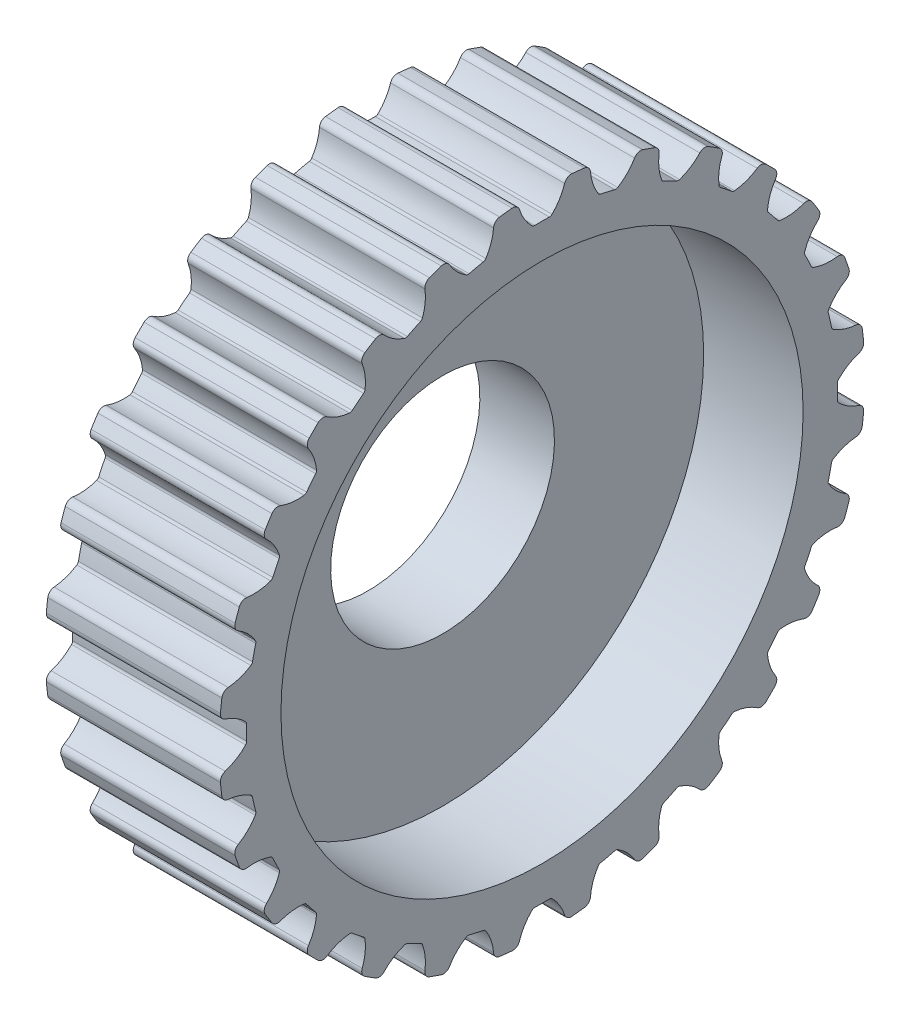
SolidWorks part; units mm, degrees
material "POM 乙缩醛共聚物"
ref_plane "前视基准面" through (0, 0, 0) normal (0, 0, 1) x (1, 0, 0)
ref_plane "上视基准面" through (0, 0, 0) normal (0, 1, 0) x (1, 0, 0)
ref_plane "右视基准面" through (0, 0, 0) normal (1, 0, 0) x (0, 0, -1)
ref_plane "基准面1" through (0, 0, 0) normal (0, 0, 1) x (1, 0, 0)
sketch "草图1" plane through (0, 0, 0) normal (0, 0, 1) x (1, 0, 0)
  line L0 (0, 0) -> (0, 10)
  line L1 (0, 10) -> (1, 10)
  line L2 (1, 10) -> (1, 12.8583)
  line L3 (1, 12.8583) -> (0.4955, 14.7412)
  line L4 (0.4955, 14.7412) -> (1.4614, 15)
  line L5 (1.4614, 15) -> (2, 12.99)
  line L6 (2, 12.99) -> (9, 12.99)
  line L7 (9, 12.99) -> (9.5386, 15)
  line L8 (9.5386, 15) -> (10.5045, 14.7412)
  line L9 (10.5045, 14.7412) -> (10, 12.8583)
  line L10 (10, 12.8583) -> (10, 10)
  line L11 (10, 10) -> (11, 10)
  line L12 (11, 10) -> (11, 0)
  line L13 (11, 0) -> (0, 0)
  line L14 (11, 0) -> (0, 0) construction
revolve "旋转1" add sketch "草图1" angle 360 about L14 reverse direction yes
ref_plane "基准面2" through (0, 0, 0) normal (0, 0, 1) x (1, 0, 0)
hole_wizard "孔1" positions "草图3" profile "草图2" legacy
sketch "草图3" plane through (11, 0, 0) normal (1, 0, 0) x (0, 0, -1)
  point P0 (0, 0)
sketch "草图2" plane through (11, 0, 0) normal (0, 1, 0) x (0, 0, -1)
  line L0 (0, 0) -> (0, 11)
  line L1 (0, 11) -> (4.5, 11)
  line L2 (4.5, 11) -> (4.5, 0)
  line L3 (4.5, 0) -> (0, 0)
  line L4 (0, 110) -> (0, -10) construction
  dimension "直径" = 9
  dimension "深度" = 11
ref_plane "基准面3" through (2, 0, 0) normal (1, 0, 0) x (0, 0, -1)
sketch "草图4" plane through (2, 0, 0) normal (1, 0, 0) x (0, 0, -1)
  circle A0 centre (0, 0) radius 17.99
  arc A1 (-12.9343, 1.2013) -> (-12.7398, 0.9084) centre (-12.6555, 1.1754) ccw
  arc A2 (-12.7398, 0.9084) -> (-11.9188, 0.4022) centre (-13.3344, -0.975) cw
  arc A3 (-11.9188, 0.4022) -> (-11.8764, 0.2939) centre (-12.0263, 0.2976) cw
  arc A4 (-11.8764, 0.2939) -> (-11.8764, -0.2939) centre (0, 0) ccw
  arc A5 (-11.8764, -0.2939) -> (-11.9188, -0.4022) centre (-12.0263, -0.2976) cw
  arc A6 (-11.9188, -0.4022) -> (-12.7398, -0.9084) centre (-13.3344, 0.975) cw
  arc A7 (-12.7398, -0.9084) -> (-12.9343, -1.2013) centre (-12.6555, -1.1754) ccw
  arc A8 (-12.9343, -1.2013) -> (-12.8774, -1.707) centre (0, 0) ccw
  arc A9 (-12.8774, -1.707) -> (-12.6225, -1.9493) centre (-12.5998, -1.6702) ccw
  arc A10 (-12.6225, -1.9493) -> (-11.7095, -2.2601) centre (-12.7831, -3.9177) cw
  arc A11 (-11.7095, -2.2601) -> (-11.644, -2.3562) centre (-11.791, -2.386) cw
  arc A12 (-11.644, -2.3562) -> (-11.5132, -2.9293) centre (0, 0) ccw
  arc A13 (-11.5132, -2.9293) -> (-11.5305, -3.0443) centre (-11.6586, -2.9663) cw
  arc A14 (-11.5305, -3.0443) -> (-12.2183, -3.7205) centre (-13.217, -2.0166) cw
  arc A15 (-12.2183, -3.7205) -> (-12.3427, -4.0493) centre (-12.0767, -3.962) ccw
  arc A16 (-12.3427, -4.0493) -> (-12.1746, -4.5297) centre (0, 0) ccw
  arc A17 (-12.1746, -4.5297) -> (-11.8723, -4.7092) centre (-11.9122, -4.432) ccw
  arc A18 (-11.8723, -4.7092) -> (-10.913, -4.809) centre (-11.5908, -6.664) cw
  arc A19 (-10.913, -4.809) -> (-10.8278, -4.8882) centre (-10.9645, -4.9499) cw
  arc A20 (-10.8278, -4.8882) -> (-10.5727, -5.4178) centre (0, 0) ccw
  arc A21 (-10.5727, -5.4178) -> (-10.564, -5.5338) centre (-10.7062, -5.4862) cw
  arc A22 (-10.564, -5.5338) -> (-11.0841, -6.346) centre (-12.4369, -4.9071) cw
  arc A23 (-11.0841, -6.346) -> (-11.1322, -6.6943) centre (-10.8923, -6.55) ccw
  arc A24 (-11.1322, -6.6943) -> (-10.8615, -7.1252) centre (0, 0) ccw
  arc A25 (-10.8615, -7.1252) -> (-10.5268, -7.233) centre (-10.6273, -6.9716) ccw
  arc A26 (-10.5268, -7.233) -> (-9.5693, -7.1168) centre (-9.8174, -9.0761) cw
  arc A27 (-9.5693, -7.1168) -> (-9.4686, -7.175) centre (-9.5881, -7.2656) cw
  arc A28 (-9.4686, -7.175) -> (-9.1021, -7.6346) centre (0, 0) ccw
  arc A29 (-9.1021, -7.6346) -> (-9.0677, -7.7457) centre (-9.217, -7.731) cw
  arc A30 (-9.0677, -7.7457) -> (-9.394, -8.6534) centre (-11.0332, -7.5516) cw
  arc A31 (-9.394, -8.6534) -> (-9.3635, -9.0036) centre (-9.1617, -8.8096) ccw
  arc A32 (-9.3635, -9.0036) -> (-9.0036, -9.3635) centre (0, 0) ccw
  arc A33 (-9.0036, -9.3635) -> (-8.6534, -9.394) centre (-8.8096, -9.1617) ccw
  arc A34 (-8.6534, -9.394) -> (-7.7457, -9.0677) centre (-7.5516, -11.0332) cw
  arc A35 (-7.7457, -9.0677) -> (-7.6346, -9.1021) centre (-7.731, -9.217) cw
  arc A36 (-7.6346, -9.1021) -> (-7.175, -9.4686) centre (0, 0) ccw
  arc A37 (-7.175, -9.4686) -> (-7.1168, -9.5693) centre (-7.2656, -9.5881) cw
  arc A38 (-7.1168, -9.5693) -> (-7.233, -10.5268) centre (-9.0761, -9.8174) cw
  arc A39 (-7.233, -10.5268) -> (-7.1252, -10.8615) centre (-6.9716, -10.6273) ccw
  arc A40 (-7.1252, -10.8615) -> (-6.6943, -11.1322) centre (0, 0) ccw
  arc A41 (-6.6943, -11.1322) -> (-6.346, -11.0841) centre (-6.55, -10.8923) ccw
  arc A42 (-6.346, -11.0841) -> (-5.5338, -10.564) centre (-4.9071, -12.4369) cw
  arc A43 (-5.5338, -10.564) -> (-5.4178, -10.5727) centre (-5.4862, -10.7062) cw
  arc A44 (-5.4178, -10.5727) -> (-4.8882, -10.8278) centre (0, 0) ccw
  arc A45 (-4.8882, -10.8278) -> (-4.809, -10.913) centre (-4.9499, -10.9645) cw
  arc A46 (-4.809, -10.913) -> (-4.7092, -11.8723) centre (-6.664, -11.5908) cw
  arc A47 (-4.7092, -11.8723) -> (-4.5297, -12.1746) centre (-4.432, -11.9122) ccw
  arc A48 (-4.5297, -12.1746) -> (-4.0493, -12.3427) centre (0, 0) ccw
  arc A49 (-4.0493, -12.3427) -> (-3.7205, -12.2183) centre (-3.962, -12.0767) ccw
  arc A50 (-3.7205, -12.2183) -> (-3.0443, -11.5305) centre (-2.0166, -13.217) cw
  arc A51 (-3.0443, -11.5305) -> (-2.9293, -11.5132) centre (-2.9663, -11.6586) cw
  arc A52 (-2.9293, -11.5132) -> (-2.3562, -11.644) centre (0, 0) ccw
  arc A53 (-2.3562, -11.644) -> (-2.2601, -11.7095) centre (-2.386, -11.791) cw
  arc A54 (-2.2601, -11.7095) -> (-1.9493, -12.6225) centre (-3.9177, -12.7831) cw
  arc A55 (-1.9493, -12.6225) -> (-1.707, -12.8774) centre (-1.6702, -12.5998) ccw
  arc A56 (-1.707, -12.8774) -> (-1.2013, -12.9343) centre (0, 0) ccw
  arc A57 (-1.2013, -12.9343) -> (-0.9084, -12.7398) centre (-1.1754, -12.6555) ccw
  arc A58 (-0.9084, -12.7398) -> (-0.4022, -11.9188) centre (0.975, -13.3344) cw
  arc A59 (-0.4022, -11.9188) -> (-0.2939, -11.8764) centre (-0.2976, -12.0263) cw
  arc A60 (-0.2939, -11.8764) -> (0.2939, -11.8764) centre (0, 0) ccw
  arc A61 (0.2939, -11.8764) -> (0.4022, -11.9188) centre (0.2976, -12.0263) cw
  arc A62 (0.4022, -11.9188) -> (0.9084, -12.7398) centre (-0.975, -13.3344) cw
  arc A63 (0.9084, -12.7398) -> (1.2013, -12.9343) centre (1.1754, -12.6555) ccw
  arc A64 (1.2013, -12.9343) -> (1.707, -12.8774) centre (0, 0) ccw
  arc A65 (1.707, -12.8774) -> (1.9493, -12.6225) centre (1.6702, -12.5998) ccw
  arc A66 (1.9493, -12.6225) -> (2.2601, -11.7095) centre (3.9177, -12.7831) cw
  arc A67 (2.2601, -11.7095) -> (2.3562, -11.644) centre (2.386, -11.791) cw
  arc A68 (2.3562, -11.644) -> (2.9293, -11.5132) centre (0, 0) ccw
  arc A69 (2.9293, -11.5132) -> (3.0443, -11.5305) centre (2.9663, -11.6586) cw
  arc A70 (3.0443, -11.5305) -> (3.7205, -12.2183) centre (2.0166, -13.217) cw
  arc A71 (3.7205, -12.2183) -> (4.0493, -12.3427) centre (3.962, -12.0767) ccw
  arc A72 (4.0493, -12.3427) -> (4.5297, -12.1746) centre (0, 0) ccw
  arc A73 (4.5297, -12.1746) -> (4.7092, -11.8723) centre (4.432, -11.9122) ccw
  arc A74 (4.7092, -11.8723) -> (4.809, -10.913) centre (6.664, -11.5908) cw
  arc A75 (4.809, -10.913) -> (4.8882, -10.8278) centre (4.9499, -10.9645) cw
  arc A76 (4.8882, -10.8278) -> (5.4178, -10.5727) centre (0, 0) ccw
  arc A77 (5.4178, -10.5727) -> (5.5338, -10.564) centre (5.4862, -10.7062) cw
  arc A78 (5.5338, -10.564) -> (6.346, -11.0841) centre (4.9071, -12.4369) cw
  arc A79 (6.346, -11.0841) -> (6.6943, -11.1322) centre (6.55, -10.8923) ccw
  arc A80 (6.6943, -11.1322) -> (7.1252, -10.8615) centre (0, 0) ccw
  arc A81 (7.1252, -10.8615) -> (7.233, -10.5268) centre (6.9716, -10.6273) ccw
  arc A82 (7.233, -10.5268) -> (7.1168, -9.5693) centre (9.0761, -9.8174) cw
  arc A83 (7.1168, -9.5693) -> (7.175, -9.4686) centre (7.2656, -9.5881) cw
  arc A84 (7.175, -9.4686) -> (7.6346, -9.1021) centre (0, 0) ccw
  arc A85 (7.6346, -9.1021) -> (7.7457, -9.0677) centre (7.731, -9.217) cw
  arc A86 (7.7457, -9.0677) -> (8.6534, -9.394) centre (7.5516, -11.0332) cw
  arc A87 (8.6534, -9.394) -> (9.0036, -9.3635) centre (8.8096, -9.1617) ccw
  arc A88 (9.0036, -9.3635) -> (9.3635, -9.0036) centre (0, 0) ccw
  arc A89 (9.3635, -9.0036) -> (9.394, -8.6534) centre (9.1617, -8.8096) ccw
  arc A90 (9.394, -8.6534) -> (9.0677, -7.7457) centre (11.0332, -7.5516) cw
  arc A91 (9.0677, -7.7457) -> (9.1021, -7.6346) centre (9.217, -7.731) cw
  arc A92 (9.1021, -7.6346) -> (9.4686, -7.175) centre (0, 0) ccw
  arc A93 (9.4686, -7.175) -> (9.5693, -7.1168) centre (9.5881, -7.2656) cw
  arc A94 (9.5693, -7.1168) -> (10.5268, -7.233) centre (9.8174, -9.0761) cw
  arc A95 (10.5268, -7.233) -> (10.8615, -7.1252) centre (10.6273, -6.9716) ccw
  arc A96 (10.8615, -7.1252) -> (11.1322, -6.6943) centre (0, 0) ccw
  arc A97 (11.1322, -6.6943) -> (11.0841, -6.346) centre (10.8923, -6.55) ccw
  arc A98 (11.0841, -6.346) -> (10.564, -5.5338) centre (12.4369, -4.9071) cw
  arc A99 (10.564, -5.5338) -> (10.5727, -5.4178) centre (10.7062, -5.4862) cw
  arc A100 (10.5727, -5.4178) -> (10.8278, -4.8882) centre (0, 0) ccw
  arc A101 (10.8278, -4.8882) -> (10.913, -4.809) centre (10.9645, -4.9499) cw
  arc A102 (10.913, -4.809) -> (11.8723, -4.7092) centre (11.5908, -6.664) cw
  arc A103 (11.8723, -4.7092) -> (12.1746, -4.5297) centre (11.9122, -4.432) ccw
  arc A104 (12.1746, -4.5297) -> (12.3427, -4.0493) centre (0, 0) ccw
  arc A105 (12.3427, -4.0493) -> (12.2183, -3.7205) centre (12.0767, -3.962) ccw
  arc A106 (12.2183, -3.7205) -> (11.5305, -3.0443) centre (13.217, -2.0166) cw
  arc A107 (11.5305, -3.0443) -> (11.5132, -2.9293) centre (11.6586, -2.9663) cw
  arc A108 (11.5132, -2.9293) -> (11.644, -2.3562) centre (0, 0) ccw
  arc A109 (11.644, -2.3562) -> (11.7095, -2.2601) centre (11.791, -2.386) cw
  arc A110 (11.7095, -2.2601) -> (12.6225, -1.9493) centre (12.7831, -3.9177) cw
  arc A111 (12.6225, -1.9493) -> (12.8774, -1.707) centre (12.5998, -1.6702) ccw
  arc A112 (12.8774, -1.707) -> (12.9343, -1.2013) centre (0, 0) ccw
  arc A113 (12.9343, -1.2013) -> (12.7398, -0.9084) centre (12.6555, -1.1754) ccw
  arc A114 (12.7398, -0.9084) -> (11.9188, -0.4022) centre (13.3344, 0.975) cw
  arc A115 (11.9188, -0.4022) -> (11.8764, -0.2939) centre (12.0263, -0.2976) cw
  arc A116 (11.8764, -0.2939) -> (11.8764, 0.2939) centre (0, 0) ccw
  arc A117 (11.8764, 0.2939) -> (11.9188, 0.4022) centre (12.0263, 0.2976) cw
  arc A118 (11.9188, 0.4022) -> (12.7398, 0.9084) centre (13.3344, -0.975) cw
  arc A119 (12.7398, 0.9084) -> (12.9343, 1.2013) centre (12.6555, 1.1754) ccw
  arc A120 (12.9343, 1.2013) -> (12.8774, 1.707) centre (0, 0) ccw
  arc A121 (12.8774, 1.707) -> (12.6225, 1.9493) centre (12.5998, 1.6702) ccw
  arc A122 (12.6225, 1.9493) -> (11.7095, 2.2601) centre (12.7831, 3.9177) cw
  arc A123 (11.7095, 2.2601) -> (11.644, 2.3562) centre (11.791, 2.386) cw
  arc A124 (11.644, 2.3562) -> (11.5132, 2.9293) centre (0, 0) ccw
  arc A125 (11.5132, 2.9293) -> (11.5305, 3.0443) centre (11.6586, 2.9663) cw
  arc A126 (11.5305, 3.0443) -> (12.2183, 3.7205) centre (13.217, 2.0166) cw
  arc A127 (12.2183, 3.7205) -> (12.3427, 4.0493) centre (12.0767, 3.962) ccw
  arc A128 (12.3427, 4.0493) -> (12.1746, 4.5297) centre (0, 0) ccw
  arc A129 (12.1746, 4.5297) -> (11.8723, 4.7092) centre (11.9122, 4.432) ccw
  arc A130 (11.8723, 4.7092) -> (10.913, 4.809) centre (11.5908, 6.664) cw
  arc A131 (10.913, 4.809) -> (10.8278, 4.8882) centre (10.9645, 4.9499) cw
  arc A132 (10.8278, 4.8882) -> (10.5727, 5.4178) centre (0, 0) ccw
  arc A133 (10.5727, 5.4178) -> (10.564, 5.5338) centre (10.7062, 5.4862) cw
  arc A134 (10.564, 5.5338) -> (11.0841, 6.346) centre (12.4369, 4.9071) cw
  arc A135 (11.0841, 6.346) -> (11.1322, 6.6943) centre (10.8923, 6.55) ccw
  arc A136 (11.1322, 6.6943) -> (10.8615, 7.1252) centre (0, 0) ccw
  arc A137 (10.8615, 7.1252) -> (10.5268, 7.233) centre (10.6273, 6.9716) ccw
  arc A138 (10.5268, 7.233) -> (9.5693, 7.1168) centre (9.8174, 9.0761) cw
  arc A139 (9.5693, 7.1168) -> (9.4686, 7.175) centre (9.5881, 7.2656) cw
  arc A140 (9.4686, 7.175) -> (9.1021, 7.6346) centre (0, 0) ccw
  arc A141 (9.1021, 7.6346) -> (9.0677, 7.7457) centre (9.217, 7.731) cw
  arc A142 (9.0677, 7.7457) -> (9.394, 8.6534) centre (11.0332, 7.5516) cw
  arc A143 (9.394, 8.6534) -> (9.3635, 9.0036) centre (9.1617, 8.8096) ccw
  arc A144 (9.3635, 9.0036) -> (9.0036, 9.3635) centre (0, 0) ccw
  arc A145 (9.0036, 9.3635) -> (8.6534, 9.394) centre (8.8096, 9.1617) ccw
  arc A146 (8.6534, 9.394) -> (7.7457, 9.0677) centre (7.5516, 11.0332) cw
  arc A147 (7.7457, 9.0677) -> (7.6346, 9.1021) centre (7.731, 9.217) cw
  arc A148 (7.6346, 9.1021) -> (7.175, 9.4686) centre (0, 0) ccw
  arc A149 (7.175, 9.4686) -> (7.1168, 9.5693) centre (7.2656, 9.5881) cw
  arc A150 (7.1168, 9.5693) -> (7.233, 10.5268) centre (9.0761, 9.8174) cw
  arc A151 (7.233, 10.5268) -> (7.1252, 10.8615) centre (6.9716, 10.6273) ccw
  arc A152 (7.1252, 10.8615) -> (6.6943, 11.1322) centre (0, 0) ccw
  arc A153 (6.6943, 11.1322) -> (6.346, 11.0841) centre (6.55, 10.8923) ccw
  arc A154 (6.346, 11.0841) -> (5.5338, 10.564) centre (4.9071, 12.4369) cw
  arc A155 (5.5338, 10.564) -> (5.4178, 10.5727) centre (5.4862, 10.7062) cw
  arc A156 (5.4178, 10.5727) -> (4.8882, 10.8278) centre (0, 0) ccw
  arc A157 (4.8882, 10.8278) -> (4.809, 10.913) centre (4.9499, 10.9645) cw
  arc A158 (4.809, 10.913) -> (4.7092, 11.8723) centre (6.664, 11.5908) cw
  arc A159 (4.7092, 11.8723) -> (4.5297, 12.1746) centre (4.432, 11.9122) ccw
  arc A160 (4.5297, 12.1746) -> (4.0493, 12.3427) centre (0, 0) ccw
  arc A161 (4.0493, 12.3427) -> (3.7205, 12.2183) centre (3.962, 12.0767) ccw
  arc A162 (3.7205, 12.2183) -> (3.0443, 11.5305) centre (2.0166, 13.217) cw
  arc A163 (3.0443, 11.5305) -> (2.9293, 11.5132) centre (2.9663, 11.6586) cw
  arc A164 (2.9293, 11.5132) -> (2.3562, 11.644) centre (0, 0) ccw
  arc A165 (2.3562, 11.644) -> (2.2601, 11.7095) centre (2.386, 11.791) cw
  arc A166 (2.2601, 11.7095) -> (1.9493, 12.6225) centre (3.9177, 12.7831) cw
  arc A167 (1.9493, 12.6225) -> (1.707, 12.8774) centre (1.6702, 12.5998) ccw
  arc A168 (1.707, 12.8774) -> (1.2013, 12.9343) centre (0, 0) ccw
  arc A169 (1.2013, 12.9343) -> (0.9084, 12.7398) centre (1.1754, 12.6555) ccw
  arc A170 (0.9084, 12.7398) -> (0.4022, 11.9188) centre (-0.975, 13.3344) cw
  arc A171 (0.4022, 11.9188) -> (0.2939, 11.8764) centre (0.2976, 12.0263) cw
  arc A172 (0.2939, 11.8764) -> (-0.2939, 11.8764) centre (0, 0) ccw
  arc A173 (-0.2939, 11.8764) -> (-0.4022, 11.9188) centre (-0.2976, 12.0263) cw
  arc A174 (-0.4022, 11.9188) -> (-0.9084, 12.7398) centre (0.975, 13.3344) cw
  arc A175 (-0.9084, 12.7398) -> (-1.2013, 12.9343) centre (-1.1754, 12.6555) ccw
  arc A176 (-1.2013, 12.9343) -> (-1.707, 12.8774) centre (0, 0) ccw
  arc A177 (-1.707, 12.8774) -> (-1.9493, 12.6225) centre (-1.6702, 12.5998) ccw
  arc A178 (-1.9493, 12.6225) -> (-2.2601, 11.7095) centre (-3.9177, 12.7831) cw
  arc A179 (-2.2601, 11.7095) -> (-2.3562, 11.644) centre (-2.386, 11.791) cw
  arc A180 (-2.3562, 11.644) -> (-2.9293, 11.5132) centre (0, 0) ccw
  arc A181 (-2.9293, 11.5132) -> (-3.0443, 11.5305) centre (-2.9663, 11.6586) cw
  arc A182 (-3.0443, 11.5305) -> (-3.7205, 12.2183) centre (-2.0166, 13.217) cw
  arc A183 (-3.7205, 12.2183) -> (-4.0493, 12.3427) centre (-3.962, 12.0767) ccw
  arc A184 (-4.0493, 12.3427) -> (-4.5297, 12.1746) centre (0, 0) ccw
  arc A185 (-4.5297, 12.1746) -> (-4.7092, 11.8723) centre (-4.432, 11.9122) ccw
  arc A186 (-4.7092, 11.8723) -> (-4.809, 10.913) centre (-6.664, 11.5908) cw
  arc A187 (-4.809, 10.913) -> (-4.8882, 10.8278) centre (-4.9499, 10.9645) cw
  arc A188 (-4.8882, 10.8278) -> (-5.4178, 10.5727) centre (0, 0) ccw
  arc A189 (-5.4178, 10.5727) -> (-5.5338, 10.564) centre (-5.4862, 10.7062) cw
  arc A190 (-5.5338, 10.564) -> (-6.346, 11.0841) centre (-4.9071, 12.4369) cw
  arc A191 (-6.346, 11.0841) -> (-6.6943, 11.1322) centre (-6.55, 10.8923) ccw
  arc A192 (-6.6943, 11.1322) -> (-7.1252, 10.8615) centre (0, 0) ccw
  arc A193 (-7.1252, 10.8615) -> (-7.233, 10.5268) centre (-6.9716, 10.6273) ccw
  arc A194 (-7.233, 10.5268) -> (-7.1168, 9.5693) centre (-9.0761, 9.8174) cw
  arc A195 (-7.1168, 9.5693) -> (-7.175, 9.4686) centre (-7.2656, 9.5881) cw
  arc A196 (-7.175, 9.4686) -> (-7.6346, 9.1021) centre (0, 0) ccw
  arc A197 (-7.6346, 9.1021) -> (-7.7457, 9.0677) centre (-7.731, 9.217) cw
  arc A198 (-7.7457, 9.0677) -> (-8.6534, 9.394) centre (-7.5516, 11.0332) cw
  arc A199 (-8.6534, 9.394) -> (-9.0036, 9.3635) centre (-8.8096, 9.1617) ccw
  arc A200 (-9.0036, 9.3635) -> (-9.3635, 9.0036) centre (0, 0) ccw
  arc A201 (-9.3635, 9.0036) -> (-9.394, 8.6534) centre (-9.1617, 8.8096) ccw
  arc A202 (-9.394, 8.6534) -> (-9.0677, 7.7457) centre (-11.0332, 7.5516) cw
  arc A203 (-9.0677, 7.7457) -> (-9.1021, 7.6346) centre (-9.217, 7.731) cw
  arc A204 (-9.1021, 7.6346) -> (-9.4686, 7.175) centre (0, 0) ccw
  arc A205 (-9.4686, 7.175) -> (-9.5693, 7.1168) centre (-9.5881, 7.2656) cw
  arc A206 (-9.5693, 7.1168) -> (-10.5268, 7.233) centre (-9.8174, 9.0761) cw
  arc A207 (-10.5268, 7.233) -> (-10.8615, 7.1252) centre (-10.6273, 6.9716) ccw
  arc A208 (-10.8615, 7.1252) -> (-11.1322, 6.6943) centre (0, 0) ccw
  arc A209 (-11.1322, 6.6943) -> (-11.0841, 6.346) centre (-10.8923, 6.55) ccw
  arc A210 (-11.0841, 6.346) -> (-10.564, 5.5338) centre (-12.4369, 4.9071) cw
  arc A211 (-10.564, 5.5338) -> (-10.5727, 5.4178) centre (-10.7062, 5.4862) cw
  arc A212 (-10.5727, 5.4178) -> (-10.8278, 4.8882) centre (0, 0) ccw
  arc A213 (-10.8278, 4.8882) -> (-10.913, 4.809) centre (-10.9645, 4.9499) cw
  arc A214 (-10.913, 4.809) -> (-11.8723, 4.7092) centre (-11.5908, 6.664) cw
  arc A215 (-11.8723, 4.7092) -> (-12.1746, 4.5297) centre (-11.9122, 4.432) ccw
  arc A216 (-12.1746, 4.5297) -> (-12.3427, 4.0493) centre (0, 0) ccw
  arc A217 (-12.3427, 4.0493) -> (-12.2183, 3.7205) centre (-12.0767, 3.962) ccw
  arc A218 (-12.2183, 3.7205) -> (-11.5305, 3.0443) centre (-13.217, 2.0166) cw
  arc A219 (-11.5305, 3.0443) -> (-11.5132, 2.9293) centre (-11.6586, 2.9663) cw
  arc A220 (-11.5132, 2.9293) -> (-11.644, 2.3562) centre (0, 0) ccw
  arc A221 (-11.644, 2.3562) -> (-11.7095, 2.2601) centre (-11.791, 2.386) cw
  arc A222 (-11.7095, 2.2601) -> (-12.6225, 1.9493) centre (-12.7831, 3.9177) cw
  arc A223 (-12.6225, 1.9493) -> (-12.8774, 1.707) centre (-12.5998, 1.6702) ccw
  arc A224 (-12.8774, 1.707) -> (-12.9343, 1.2013) centre (0, 0) ccw
extrude "切除-拉伸1" cut sketch "草图4" along normal blind 7
ref_plane "基准面4" through (0, 0, 0) normal (0, 0, 1) x (1, 0, 0)
ref_plane "基准面5" through (5.5, 0, 0) normal (1, 0, 0) x (0, 0, -1)
ref_plane "to_belt XY" through (5.5, 0, 0) normal (-1, 0, 0) x (0, 0, 1)
ref_plane "to_belt XZ" through (0, 0, 0) normal (0, 1, 0) x (1, 0, 0)
ref_plane "to_belt YZ" through (0, 0, 0) normal (0, 0, -1) x (-1, 0, 0)
ref_axis "to_belt X" through (5.5, 0, 80.9) along (0, 0, -1)
ref_axis "to_belt Y" through (5.5, 50, 0) along (0, -1, 0)
ref_axis "to_belt Z" through (-80.9, 0, 0) along (1, 0, 0)
sketch3d "to_belt"
  point P0 (5.5, 0, 0)
sketch "草图5" plane through (0, 0, 0) normal (0, 0, 1) x (1, 0, 0)
  line L1 (-10.5886, 18.7406) -> (2, 18.7406)
  line L2 (-10.5886, 18.7406) -> (-10.5886, -21.2299)
  line L3 (-10.5886, -21.2299) -> (2, -21.2299)
  line L4 (2, 18.7406) -> (2, -21.2299)
  line L5 (9, -22.5101) -> (34.675, -22.5101)
  line L6 (9, -22.5101) -> (9, 27.6308)
  line L7 (9, 27.6308) -> (34.675, 27.6308)
  line L8 (34.675, -22.5101) -> (34.675, 27.6308)
extrude "切除-拉伸2" cut sketch "草图5" against normal through all both and the other way through all
sketch "草图6" plane through (9, 0, 0) normal (1, 0, 0) x (0, 0, -1)
  circle A0 centre (0, 0) radius 10.5
  dimension "D1" = 21
extrude "切除-拉伸3" cut sketch "草图6" against normal offset from surface (4 mm away) 3 up to face at (2, 0, 0)
